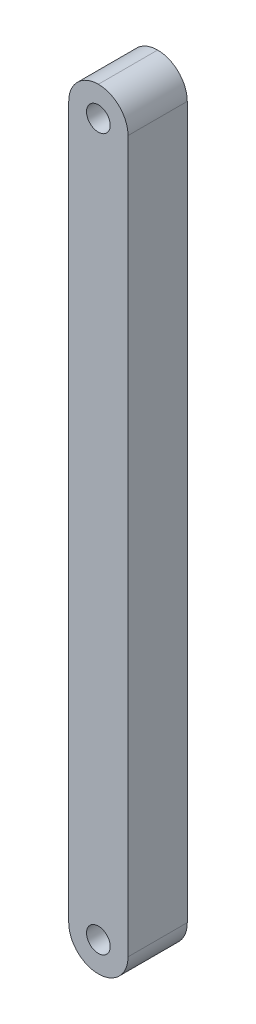
SolidWorks part; units mm, degrees
ref_plane "Front" through (0, 0, 0) normal (0, 0, 1) x (1, 0, 0)
ref_plane "Top" through (0, 0, 0) normal (0, 1, 0) x (1, 0, 0)
ref_plane "Right" through (0, 0, 0) normal (1, 0, 0) x (0, 0, -1)
sketch "Esquisse1" plane through (0, 0, 0) normal (0, 0, 1) x (1, 0, 0)
  line L1 (0, 0) -> (10, 0)
  line L2 (0, 0) -> (0, 130)
  line L3 (0, 130) -> (10, 130)
  line L4 (10, 0) -> (10, 130)
  dimension "D1" = 10
  dimension "D2" = 130
extrude "Boss.-Extru.1" add sketch "Esquisse1" along normal blind 10
sketch "Esquisse2" plane through (0, 0, 10) normal (0, 0, 1) x (1, 0, 0)
  line L0 (5, 125) -> (5, 130) construction
  line L1 (10, 130) -> (0, 130) construction
  line L2 (0, 0) -> (10, 0) construction
  line L3 (5, 5) -> (5, 0) construction
  line L4 (5, 130) -> (28.6044, 85) construction
  circle A1 centre (5, 125) radius 2
  circle A2 centre (5, 5) radius 2
  point P11 (5, 0)
  dimension "D2" = 5
  dimension "D3" = 4
  dimension "D4" = 4
  dimension "D5" = 5
extrude "Enlèv. mat.-Extru.1" cut sketch "Esquisse2" against normal up to vertex (10 mm away) up to point (0, 130, 0)
fillet "Congé1" radius 5 4 edges at (10, 130, 5) (0, 130, 5) (10, 0, 5) (0, 0, 5)
